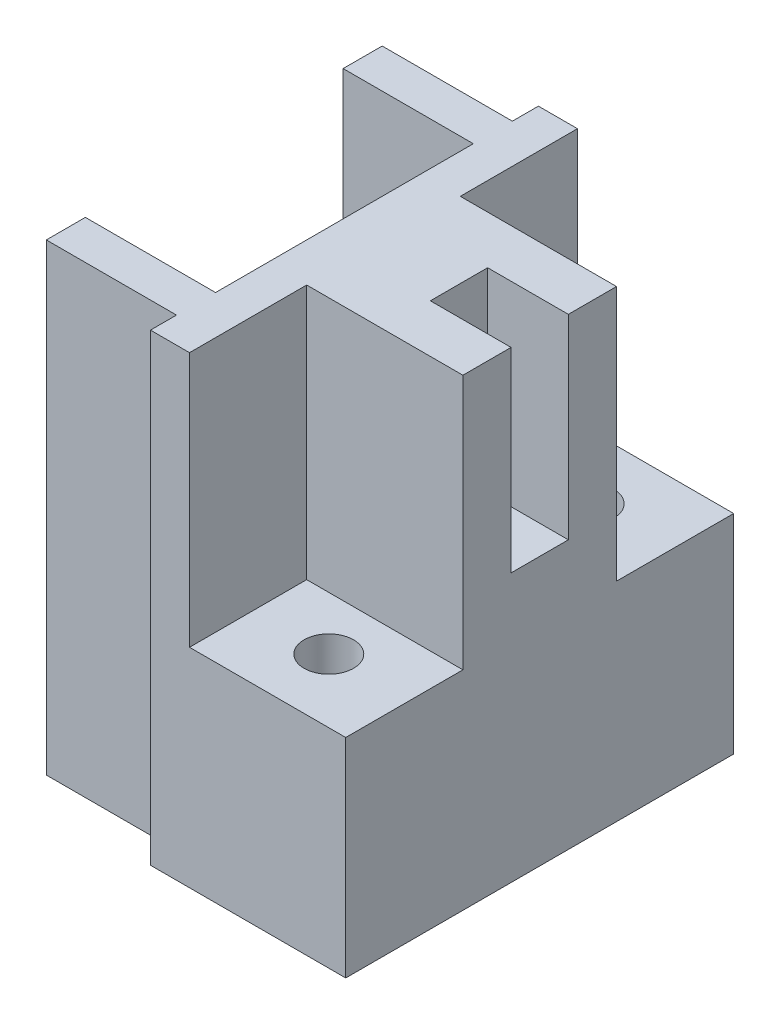
SolidWorks part; units mm, degrees
ref_plane "Front Plane" through (0, 0, 0) normal (0, 0, 1) x (1, 0, 0)
ref_plane "Top Plane" through (0, 0, 0) normal (0, 1, 0) x (1, 0, 0)
ref_plane "Right Plane" through (0, 0, 0) normal (1, 0, 0) x (0, 0, -1)
sketch "Sketch1" plane through (0, 0, 0) normal (0, 1, 0) x (1, 0, 0)
  line L0 (40.2517, 37.2145) -> (40.2517, -0.6315)
  line L1 (40.2517, 37.2145) -> (21.2017, 37.2145)
  line L2 (21.2017, 37.2145) -> (21.2017, -0.6315)
  line L3 (21.2017, -0.6315) -> (40.2517, -0.6315)
  line L4 (21.2017, 34.6745) -> (8.5017, 34.6745)
  line L5 (8.5017, 34.6745) -> (8.5017, 30.8645)
  line L6 (8.5017, 30.8645) -> (21.2017, 30.8645)
  line L7 (21.2017, 1.9085) -> (8.5017, 1.9085)
  line L8 (8.5017, 1.9085) -> (8.5017, 5.7185)
  line L9 (8.5017, 5.7185) -> (21.2017, 5.7185)
  line L10 (21.2017, 18.2915) -> (40.2517, 18.2915)
  line L11 (40.2517, 21.0855) -> (32.3777, 21.0855)
  line L12 (32.3777, 21.0855) -> (32.3777, 15.4975)
  line L13 (32.3777, 15.4975) -> (40.2517, 15.4975)
  line L14 (36.3147, 21.0855) -> (36.3147, 18.2915)
  line L15 (36.3147, 18.2915) -> (36.3147, 15.4975)
  line L16 (32.3777, 30.9915) -> (32.3777, 18.2915)
  line L17 (32.3777, 18.2915) -> (32.3777, 5.5915)
  circle A0 centre (32.3777, 30.9915) radius 2.413
  circle A1 centre (32.3777, 5.5915) radius 2.413
  point P25 (22.7566, 17.7628)
  point P26 (22.7566, 13.8161)
  point P27 (0, 0)
  dimension "D11" = 4.826
  dimension "D12" = 4.826
  dimension "D1" = 2.54
  dimension "D2" = 2.54
  dimension "D3" = 3.81
  dimension "D4" = 3.81
  dimension "D5" = 37.846
  dimension "D6" = 12.7
  dimension "D7" = 12.7
  dimension "D8" = 19.05
  dimension "D9" = 5.588
  dimension "D10" = 7.874
  dimension "D13" = 12.7
  dimension "D14" = 12.7
extrude "Boss-Extrude1" add sketch "Sketch1" along normal blind 45.212 contours A1 L12 L10 L2 L3 L0 L13 | L9 L8 L7 L2 | L5 L6 L2 L4 | A0 L11 L0 L1 L2 L10 L12 region at (30.2484, 0, -28.1221) region at (14.8517, 0, -32.7695) region at (30.2484, 0, -8.4609) region at (14.8517, 0, -3.8135)
extrude "Boss-Extrude2" add sketch "Sketch1<4>" along normal blind 26.162 contours L11 L14 L10 L0 | L14 L11 L12 L10 | L15 L10 L12 L13 | L10 L15 L13 L0 region at (38.2832, 0, -19.6885) region at (38.2832, 0, -16.8945) region at (34.3462, 0, -19.6885) region at (34.3462, 0, -16.8945)
sketch "Sketch1<4>" plane through (0, 0, 0) normal (0, 1, 0) x (1, 0, 0) same geometry as "Sketch1"
sketch "Sketch2" plane through (0, 45.212, 0) normal (0, 1, 0) x (1, 0, 0)
  line L0 (40.2517, 37.2145) -> (25.0117, 37.2145)
  line L1 (40.2517, 37.2145) -> (21.2017, 37.2145) construction
  line L2 (25.0117, 37.2145) -> (25.0117, 25.7845)
  line L3 (25.0117, 25.7845) -> (40.2517, 25.7845)
  line L4 (40.2517, 37.2145) -> (40.2517, -0.6315) construction
  line L5 (40.2517, 25.7845) -> (40.2517, 37.2145)
  line L6 (40.2517, -0.6315) -> (40.2517, 10.7985)
  line L7 (40.2517, 15.4975) -> (40.2517, -0.6315) construction
  line L8 (40.2517, 10.7985) -> (25.0117, 10.7985)
  line L9 (25.0117, 10.7985) -> (25.0117, -0.6315)
  line L10 (25.0117, -0.6315) -> (40.5419, -0.6315)
  circle M5 centre (32.3777, 5.5915) radius 2.413
  line M9 (40.2517, 21.0855) -> (40.2517, 37.2145)
  line M10 (40.2517, 37.2145) -> (21.2017, 37.2145)
  line M20 (21.2017, -0.6315) -> (40.2517, -0.6315)
  line M21 (40.2517, -0.6315) -> (40.2517, 15.4975)
  circle M22 centre (32.3777, 30.9915) radius 2.413
  dimension "D1" = 11.43
  dimension "D2" = 11.43
  dimension "D3" = 15.24
  dimension "D4" = 15.24
extrude "Cut-Extrude1" cut sketch "Sketch2" against normal blind 24.892 contours L8 L9 M20 M21 M5 | L2 L3 M9 M10 M22 region at (40.0612, 45.212, -31.4995) region at (32.6317, 45.212, 0.441)
